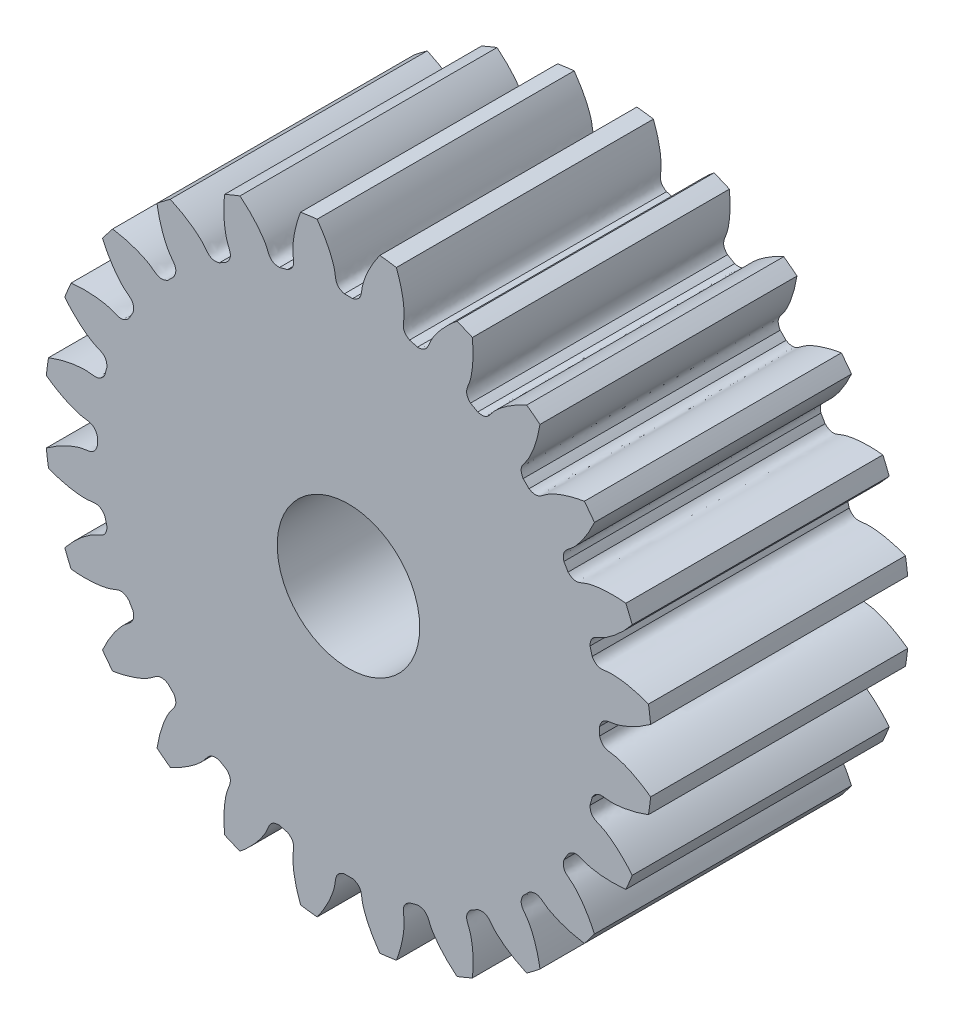
SolidWorks part; units mm, degrees
ref_plane "前视基准面" through (0, 0, 0) normal (0, 0, 1) x (1, 0, 0)
ref_plane "上视基准面" through (0, 0, 0) normal (0, 1, 0) x (1, 0, 0)
ref_plane "右视基准面" through (0, 0, 0) normal (1, 0, 0) x (0, 0, -1)
sketch "草图1" plane through (0, 0, 0) normal (0, 0, 1) x (1, 0, 0)
  circle A0 centre (0, 0) radius 6.5
extrude "凸台-拉伸1" add sketch "草图1" along normal blind 5.5
ref_axis "基准轴1" through (0, 0, 5.5) along (0, 0, -1)
sketch "草图2" plane through (0, 0, 0) normal (0, 0, 1) x (1, 0, 0)
  line L0 (0, 0) -> (0, 6.5) construction
  circle A0 centre (0, 0) radius 6.5 construction
  arc A1 (0.0884, 5.3743) -> (-0.0884, 5.3743) centre (0, 0) ccw
  arc A2 (1.5578, 7.3471) -> (-1.5578, 7.3471) centre (0, 0) ccw
  spline S0 degree 3 poles (0.0884, 5.3743) (0.284, 5.4284) (0.2695, 5.5579) (0.2931, 5.6863) (0.2965, 5.7029) (0.3007, 5.7216) (0.3058, 5.7424) (0.312, 5.7653) (0.3191, 5.7902) (0.3275, 5.8171) (0.3371, 5.846) (0.348, 5.8769) (0.3604, 5.9096) (0.3742, 5.9441) (0.3896, 5.9805) (0.4067, 6.0185) (0.4254, 6.0583) (0.446, 6.0997) (0.4684, 6.1427) (0.4928, 6.1872) (0.5192, 6.2332) (0.5476, 6.2806) (0.5782, 6.3293) (0.611, 6.3792) (0.6461, 6.4304) (0.6834, 6.4827) (0.7232, 6.536) (0.7654, 6.5903) (0.8101, 6.6456) (0.8574, 6.7016) (0.9073, 6.7583) (0.9598, 6.8158) (1.015, 6.8738) (1.0729, 6.9322) (1.1336, 6.9911) (1.1972, 7.0503) (1.2635, 7.1097) (1.3328, 7.1693) (1.4302, 7.2497) (1.506, 7.3084) (1.5578, 7.3471) knots 0 0 0 0 0.143961 0.149818 0.156577 0.164236 0.172796 0.182258 0.19262 0.203884 0.216049 0.229115 0.243082 0.25795 0.273719 0.290389 0.30796 0.326433 0.345806 0.366081 0.387257 0.409333 0.432311 0.45619 0.48097 0.506651 0.533234 0.560717 0.589101 0.618387 0.648574 0.679661 0.71165 0.74454 0.778331 0.813023 0.848616 0.885111 0.922506 1 1 1 1
  spline S1 degree 3 poles (-0.0884, 5.3743) (-0.284, 5.4284) (-0.2695, 5.5579) (-0.2931, 5.6863) (-0.2965, 5.7029) (-0.3007, 5.7216) (-0.3058, 5.7424) (-0.312, 5.7653) (-0.3191, 5.7902) (-0.3275, 5.8171) (-0.3371, 5.846) (-0.348, 5.8769) (-0.3604, 5.9096) (-0.3742, 5.9441) (-0.3896, 5.9805) (-0.4067, 6.0185) (-0.4254, 6.0583) (-0.446, 6.0997) (-0.4684, 6.1427) (-0.4928, 6.1872) (-0.5192, 6.2332) (-0.5476, 6.2806) (-0.5782, 6.3293) (-0.611, 6.3792) (-0.6461, 6.4304) (-0.6834, 6.4827) (-0.7232, 6.536) (-0.7654, 6.5903) (-0.8101, 6.6456) (-0.8574, 6.7016) (-0.9073, 6.7583) (-0.9598, 6.8158) (-1.015, 6.8738) (-1.0729, 6.9322) (-1.1336, 6.9911) (-1.1972, 7.0503) (-1.2635, 7.1097) (-1.3328, 7.1693) (-1.4302, 7.2497) (-1.506, 7.3084) (-1.5578, 7.3471) knots 0 0 0 0 0.143961 0.149818 0.156577 0.164236 0.172796 0.182258 0.19262 0.203884 0.216049 0.229115 0.243082 0.25795 0.273719 0.290389 0.30796 0.326433 0.345806 0.366081 0.387257 0.409333 0.432311 0.45619 0.48097 0.506651 0.533234 0.560717 0.589101 0.618387 0.648574 0.679661 0.71165 0.74454 0.778331 0.813023 0.848616 0.885111 0.922506 1 1 1 1
extrude "切除-拉伸1" cut sketch "草图2" along normal through all
pattern_circular "阵列(圆周)1" count 24 over 360 about axis through (0, 0, 5.5) along (0, 0, -1) of "切除-拉伸1"
sketch "草图3" plane through (0, 0, 0) normal (0, 0, 1) x (1, 0, 0)
  circle A0 centre (0, 0) radius 6 construction
  dimension "Dn" = 12
sketch "草图4" plane through (0, 0, 5.5) normal (0, 0, 1) x (1, 0, 0)
  circle A0 centre (0, 0) radius 1.525
  dimension "D1" = 3.05
extrude "切除-拉伸2" cut sketch "草图4" against normal up to next
